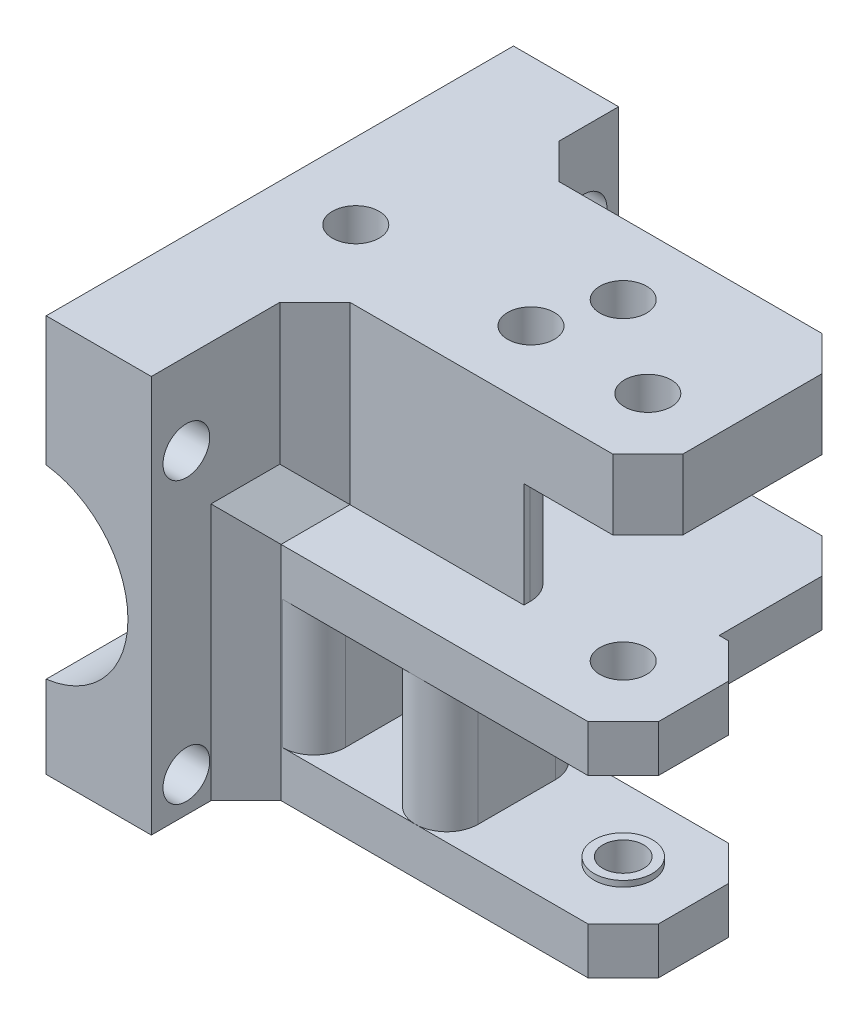
SolidWorks part; units mm, degrees
material "ABS"
ref_plane "Front Plane" through (0, 0, 0) normal (0, 0, 1) x (1, 0, 0)
ref_plane "Top Plane" through (0, 0, 0) normal (0, 1, 0) x (1, 0, 0)
ref_plane "Right Plane" through (0, 0, 0) normal (1, 0, 0) x (0, 0, -1)
sketch "Sketch1" plane through (0, 0, 0) normal (0, 0, 1) x (1, 0, 0)
  line L0 (-6.3996, -22.5) -> (56.2268, -22.5) construction
  line L1 (0, 0) -> (45, 0)
  line L2 (0, 0) -> (0, -4)
  line L3 (10, -4) -> (45, -4)
  line L4 (45, 0) -> (45, -4)
  line L5 (10, -13) -> (45, -13)
  line L7 (10, -17) -> (45, -17)
  line L8 (45, -13) -> (45, -17)
  line L9 (10, -28) -> (45, -28)
  line L10 (0, -28) -> (0, -32)
  line L11 (0, -32) -> (45, -32)
  line L12 (45, -28) -> (45, -32)
  line L13 (-6.3996, -8.5) -> (56.2268, -8.5) construction
  line L14 (0, -43.7105) -> (0, -17) construction
  line L15 (10, 15.2738) -> (10, 3.2361) construction
  line L16 (24.5, 15.2738) -> (24.5, -43.7105) construction
  line L17 (35.29, 15.2738) -> (35.29, -42.965) construction
  line L18 (0, -4) -> (0, -9)
  line L19 (0, -28) -> (0, -25)
  line L20 (10, -4) -> (10, -13)
  line L21 (10, -30.2287) -> (10, -43.7105) construction
  line L22 (10, -17) -> (10, -28) construction
  line L23 (10, -17) -> (10, -28)
  line L24 (0, -13) -> (0, 15.2738) construction
  line L25 (10, -4) -> (10, -13) construction
  arc A0 (0, -25) -> (0, -9) centre (0, -17) ccw
  dimension "D10" = 16
  dimension "D1" = 11
  dimension "D2" = 9
  dimension "D3" = 5.5
  dimension "D5" = 14
  dimension "D6" = 10
  dimension "D7" = 25.29
  dimension "D8" = 10.79
  dimension "D9" = 45
  dimension "D4" = 8.5
extrude "Boss-Extrude1" add sketch "Sketch1" along normal blind 20 and the other way blind 20
sketch "Sketch2" plane through (0, 0, 0) normal (0, 1, 0) x (1, 0, 0)
  line L0 (10, 16.1296) -> (10, -7.0419) construction
  line L1 (24.5, 13.8872) -> (24.5, -5.5077) construction
  line L2 (36.29, 12.1168) -> (36.29, -5.5077) construction
  line L3 (0, 20) -> (0, -20) construction
  line L4 (0, 0) -> (45, 0) construction
  circle A0 centre (24.5, 5.895) radius 1.75
  circle A1 centre (36.29, -5.895) radius 1.75
  dimension "D6" = 3.5
  dimension "D1" = 10
  dimension "D3" = 11.79
  dimension "D4" = 5.895
  dimension "D5" = 11.79
  dimension "D2" = 36.29
extrude "Cut-Extrude1" cut sketch "Sketch2" against normal through all
sketch "Sketch3" plane through (0, 0, 0) normal (0, 1, 0) x (1, 0, 0)
  line L0 (0, 20) -> (0, -20) construction
  circle A0 centre (7.5, 0) radius 2
  circle A1 centre (22.5, 0) radius 2
  circle A2 centre (32.5, 0) radius 2
  dimension "D1" = 7.5
  dimension "D2" = 22.5
  dimension "D3" = 32.5
  dimension "D4" = 4
extrude "Cut-Extrude2" cut sketch "Sketch3" against normal blind 7
sketch "Sketch5" plane through (0, 0, 0) normal (0, 1, 0) x (1, 0, 0)
  line L0 (10, 11.895) -> (35.5, 11.895)
  line L2 (35.5, 11.895) -> (38.5, 8.895)
  line L17 (38.5, 8.895) -> (38.5, -3)
  line L18 (38.5, -3) -> (35.5, -6)
  line L20 (10, 11.895) -> (10, 20)
  line L21 (45, 20) -> (0, 20) construction
  line L23 (10, -6) -> (10, -20)
  line L24 (45, -20) -> (0, -20) construction
  line L25 (10, -20) -> (0, -20)
  line L26 (0, -20) -> (0, 20)
  line L27 (0, 20) -> (0, -20) construction
  line L28 (0, 20) -> (10, 20)
  line L29 (10, 20) -> (45, 20)
  line L30 (35.5, -6) -> (10, -6)
  line L35 (45, 20) -> (45, -20)
  line L36 (45, -20) -> (10, -20)
  circle A0 centre (24.5, 5.895) radius 1.75 construction
  circle A1 centre (22.5, 0) radius 2 construction
  circle A2 centre (32.5, 0) radius 2 construction
  circle M28 centre (36.29, -5.895) radius 1.75
  line M30 (0, -20) -> (45, -20)
  line M31 (45, -20) -> (45, 20)
  line M32 (45, 20) -> (0, 20)
  dimension "D4" = 10
  dimension "D1" = 45
  dimension "D2" = 45
  dimension "D3" = 6
  dimension "D5" = 6
  dimension "D6" = 6
  dimension "D7" = 3
extrude "Cut-Extrude3" cut sketch "Sketch5" against normal up to next contours L23 L20 M30 M31 M32 M28 region at (10.5315, 0, -15.9475)
sketch "Sketch6" plane through (0, -13, 0) normal (0, 1, 0) x (1, 0, 0)
  line L18 (45, 20) -> (10, 20)
  line L21 (10, 20) -> (10, 11.895)
  line L22 (10, 20) -> (10, -20) construction
  line L23 (10, 11.895) -> (35.5, 11.895)
  line L24 (35.5, 11.895) -> (38.5, 8.895)
  line L25 (38.5, 8.895) -> (38.5, 0.105)
  line L26 (38.5, 0.105) -> (39.29, 0.105)
  line L27 (39.29, 0.105) -> (42.29, -2.895)
  line L28 (42.29, -2.895) -> (42.29, -8.895)
  line L29 (42.29, -8.895) -> (39.29, -11.895)
  line L30 (39.29, -11.895) -> (10, -11.895)
  line L31 (10, -11.895) -> (10, -20)
  line L32 (10, -20) -> (45, -20)
  line L33 (45, -20) -> (45, 20)
  circle A0 centre (24.5, 5.895) radius 1.75 construction
  circle A2 centre (32.5, 0) radius 2 construction
  circle A3 centre (36.29, -5.895) radius 1.75 construction
  dimension "D3" = 6
  dimension "D7" = 3
  dimension "D1" = 6
  dimension "D2" = 6
  dimension "D4" = 6
  dimension "D5" = 45
  dimension "D6" = 12
extrude "Cut-Extrude4" cut sketch "Sketch6" against normal up to next
sketch "Sketch7" plane through (0, -28, 0) normal (0, 1, 0) x (1, 0, 0)
  line L0 (10, -11.895) -> (39.29, -11.895)
  line L1 (10, 20) -> (10, -20) construction
  line L2 (10, -6) -> (10, -20) construction
  line L4 (39.29, -11.895) -> (42.29, -8.895)
  line L7 (39.29, 0.105) -> (10, 0.105)
  line L8 (10, 0.105) -> (10, 20)
  line L9 (10, 11.895) -> (10, 20) construction
  line L10 (10, 20) -> (45, 20)
  line L11 (45, 20) -> (45, -20)
  line L12 (45, -20) -> (10, -20)
  line L13 (10, -20) -> (10, -11.895)
  line L14 (42.29, -8.895) -> (42.29, -2.895)
  line L15 (42.29, -2.895) -> (39.29, 0.105)
  circle A0 centre (36.29, -5.895) radius 1.75 construction
  dimension "D3" = 6
  dimension "D1" = 6
  dimension "D2" = 6
  dimension "D4" = 225
  dimension "D5" = 3
extrude "Cut-Extrude5" cut sketch "Sketch7" against normal up to next
sketch "Sketch9" plane through (0, -13, 0) normal (0, 1, 0) x (1, 0, 0)
  line L0 (15.81, 5.895) -> (15.81, 11.895)
  line L1 (10, 11.895) -> (35.5, 11.895) construction
  line L2 (24.5, -2.795) -> (27.895, -2.795)
  line L4 (34.5432, -6) -> (10, -6) construction
  line L6 (10, -6) -> (10, 11.895)
  line L7 (10, 11.895) -> (15.81, 11.895)
  line L8 (27.895, -6) -> (27.895, -2.795)
  line L10 (27.895, -6) -> (10, -6)
  circle A0 centre (24.5, 5.895) radius 4.69 construction
  arc A1 (15.81, 5.895) -> (24.5, -2.795) centre (24.5, 5.895) ccw
  line M9 (10, 11.895) -> (10, -11.895)
  circle M11 centre (36.29, -5.895) radius 1.75
  dimension "D1" = 9.38
  dimension "D2" = 4
  dimension "D4" = 17.895
  dimension "D5" = 17.895
extrude "Boss-Extrude3" add sketch "Sketch9" along normal up to surface (9 mm away) contours A1 L0 L2 M9 M11 region at (15.5801, -13, -0.7695) up to face at (29.0994, -4, -2.0126)
sketch "Sketch10" plane through (0, -28, 0) normal (0, 1, 0) x (1, 0, 0)
  line L0 (27.19, -11.895) -> (27.19, 0.105)
  line L1 (39.29, -11.895) -> (10, -11.895) construction
  line L2 (10, 0.105) -> (39.29, 0.105) construction
  line L3 (27.19, -11.895) -> (21.81, -11.895)
  line L4 (21.81, -11.895) -> (21.81, 0.105)
  line L5 (21.81, 0.105) -> (27.19, 0.105)
  line L7 (15.81, 32.4724) -> (21.81, 32.4724) construction
  line L8 (15.81, 32.4724) -> (15.81, -20.6824) construction
  line L9 (15.81, -20.6824) -> (21.81, -20.6824) construction
  line L10 (21.81, 32.4724) -> (21.81, -20.6824) construction
  line L11 (15.81, 32.4724) -> (21.81, -20.6824) construction
  line L12 (15.81, -20.6824) -> (21.81, 32.4724) construction
  line L13 (10, -11.895) -> (15.81, -11.895)
  line L14 (10, -11.895) -> (10, 0.105)
  line L15 (10, 0.105) -> (15.81, 0.105)
  line L16 (15.81, -11.895) -> (15.81, 0.105)
  circle A0 centre (36.29, -5.895) radius 6.1 construction
  circle A1 centre (36.29, -5.895) radius 9.1 construction
  circle A2 centre (24.5, 5.895) radius 5.69 construction
  circle A3 centre (36.29, -5.895) radius 1.75 construction
  point P15 (18.81, 5.895)
  dimension "D3" = 6
  dimension "D1" = 12.2
  dimension "D2" = 3
  dimension "D4" = 17.48
extrude "Boss-Extrude4" add sketch "Sketch10" along normal up to surface (11 mm away) up to face at (32.8511, -17, 0.2983)
fillet "Fillet1" 2 edges at (27.19, -22.5, -0.105) (21.81, -22.5, -0.105) type full round first side face at (27.19, -22.5, 5.895) second side face at (21.81, -22.5, 5.895) middle face at (22.82, -24.4, -0.105)
fillet "Fillet2" 2 edges at (27.19, -22.5, 11.895) (21.81, -22.5, 11.895) type full round first side face at (27.19, -22.5, 7.24) second side face at (21.81, -22.5, 7.24) middle face at (18.81, -22.5, 11.895)
fillet "Fillet3" radius 2.69 4 edges at (15.81, -22.5, 11.895) (15.81, -22.5, -0.105) (27.895, -8.5, 2.795) (15.81, -8.5, -11.895)
chamfer "Chamfer1" distance 3 angle 45 6 edges at (10, -8.5, -11.895) (10, -17, -6) (10, -24.5, -0.105) (10, -13, 8.9475) (10, -6.5, 6) (10, -22.5, 11.895)
sketch "Sketch14" plane through (0, -17, 0) normal (0, -1, 0) x (1, 0, 0)
  circle A0 centre (36.29, 5.895) radius 2
  dimension "D1" = 4
extrude "Cut-Extrude8" cut sketch "Sketch14" against normal up to next
sketch "Sketch16" plane through (0, -4, 0) normal (0, -1, 0) x (1, 0, 0)
  circle A0 centre (24.5, -5.895) radius 2
  dimension "D1" = 4
extrude "Cut-Extrude9" cut sketch "Sketch16" against normal blind 10
sketch "Sketch17" plane through (0, -13, 0) normal (0, 1, 0) x (1, 0, 0)
  circle A0 centre (24.5, 5.895) radius 1.75
  circle A1 centre (24.5, 5.895) radius 2.5
  dimension "D1" = 5
extrude "Boss-Extrude5" add sketch "Sketch17" along normal blind 0.5
sketch "Sketch18" plane through (0, -28, 0) normal (0, 1, 0) x (1, 0, 0)
  circle A0 centre (36.29, -5.895) radius 1.75
  circle A1 centre (36.29, -5.895) radius 2.5
  dimension "D1" = 5
extrude "Boss-Extrude6" add sketch "Sketch18" along normal blind 0.5
sketch "Sketch20" plane through (0, -32, 0) normal (0, -1, 0) x (1, 0, 0)
  circle A0 centre (36.29, 5.895) radius 3
  dimension "D1" = 6
extrude "Cut-Extrude10" cut sketch "Sketch20" against normal blind 2
sketch "Sketch21" plane through (0, -17, 0) normal (0, -1, 0) x (1, 0, 0)
  circle A0 centre (24.5, -5.895) radius 3
  dimension "D1" = 6
extrude "Cut-Extrude11" cut sketch "Sketch21" against normal blind 2
sketch "Sketch11" plane through (0, 0, 0) normal (-1, 0, 0) x (0, 0, 1)
  line L0 (20, -25) -> (20, -9) construction
  line L1 (-17, -29) -> (17, -29) construction
  line L2 (-17, -29) -> (-17, -5) construction
  line L3 (-17, -5) -> (17, -5) construction
  line L4 (17, -29) -> (17, -5) construction
  line L5 (-17, -29) -> (17, -5) construction
  line L6 (-17, -5) -> (17, -29) construction
  circle A0 centre (17, -5) radius 2
  circle A1 centre (17, -29) radius 2
  circle A2 centre (-17, -29) radius 2
  circle A3 centre (-17, -5) radius 2
  point P0 (0, -17)
  point P11 (20, -17)
  dimension "D3" = 4
  dimension "D1" = 24
  dimension "D2" = 34
extrude "Cut-Extrude6" cut sketch "Sketch11" against normal blind 10
sketch "Sketch12" plane through (0, 0, 20) normal (0, 0, 1) x (1, 0, 0)
  line L0 (0, -32) -> (10, -32) construction
  line L1 (0, 0) -> (1, 0)
  line L2 (0, 0) -> (0, -32)
  line L3 (0, -32) -> (1, -32)
  line L4 (1, 0) -> (1, -32)
  dimension "D1" = 1
extrude "Cut-Extrude7" cut sketch "Sketch12" against normal through all
sketch "Sketch22" plane through (0, 0, 0) normal (0, 1, 0) x (1, 0, 0)
  line L0 (38.5, -3) -> (37.1366, -4.3634) construction
  line L1 (34.5432, -6) -> (13, -6) construction
  line L2 (37.1366, -4.3634) -> (35.5, -6)
  line L3 (35.5, -6) -> (34.5432, -6)
  arc A0 (37.1366, -4.3634) -> (34.5432, -6) centre (36.29, -5.895) ccw
  arc A1 (37.1366, -4.3634) -> (34.5432, -6) centre (36.29, -5.895) ccw construction
extrude "Boss-Extrude7" add sketch "Sketch22" against normal up to surface (4 mm away) up to face at (26.5, -4, -5.895)
sketch "Sketch23" plane through (0, 0, 0) normal (0, 1, 0) x (1, 0, 0)
  line L0 (35.5, 11.895) -> (13, 11.895)
  line L1 (13, 11.895) -> (10, 14.895)
  line L2 (10, 14.895) -> (10, 20)
  line L3 (10, 20) -> (1, 20)
  line L4 (1, 20) -> (1, -20)
  line L5 (1, -20) -> (10, -20)
  line L6 (10, -20) -> (10, -9)
  line L7 (10, -9) -> (13, -6)
  line L8 (13, -6) -> (35.5, -6)
  line L9 (35.5, -6) -> (38.5, -3)
  line L10 (38.5, -3) -> (38.5, 8.895)
  line L11 (38.5, 8.895) -> (35.5, 11.895)
  circle A0 centre (24.5, 5.895) radius 2
  circle A1 centre (32.5, 0) radius 2
  circle A2 centre (22.5, 0) radius 2
  circle A3 centre (7.5, 0) radius 2
extrude "Boss-Extrude8" add sketch "Sketch23" along normal blind 2
equation "\"D3@Sketch1\"=\"D1@Sketch1\"/2"
equation "\"D5@Sketch2\"=\"D3@Sketch2\""
equation "\"D4@Sketch2\"=\"D5@Sketch2\"/2"
equation "\"D2@Sketch5\"=\"D1@Sketch5\""
equation "\"D5@Sketch7\"=\"D3@Sketch7\"/2"
equation "\"D3@Sketch10\"=\"D2@Sketch10\"*2"
equation "\"D7@Sketch5\"=\"D5@Sketch5\"/2"
equation "\"D2@Sketch6\"=\"D1@Sketch6\""
equation "\"D3@Sketch6\"=\"D2@Sketch6\""
equation "\"D4@Sketch6\"=\"D3@Sketch6\""
